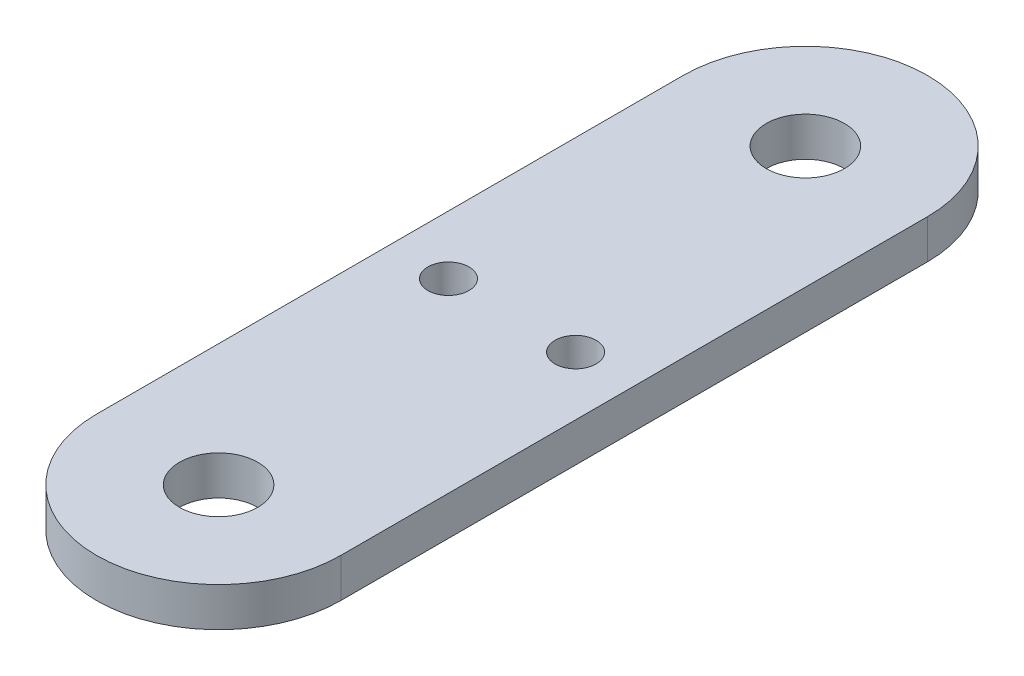
SolidWorks part; units mm, degrees
ref_plane "Front Plane" through (0, 0, 0) normal (0, 0, 1) x (1, 0, 0)
ref_plane "Top Plane" through (0, 0, 0) normal (0, 1, 0) x (1, 0, 0)
ref_plane "Right Plane" through (0, 0, 0) normal (1, 0, 0) x (0, 0, -1)
sketch "Sketch1" plane through (0, 0, 0) normal (0, 1, 0) x (1, 0, 0)
  line L0 (-6.5, 0) -> (6.5, 0) construction
  line L1 (0, 30) -> (0, -30) construction
  line L2 (12.5, -42.5) -> (-12.5, -42.5)
  line L3 (12.5, -42.5) -> (12.5, 42.5)
  line L4 (12.5, 42.5) -> (-12.5, 42.5)
  line L5 (-12.5, -42.5) -> (-12.5, 42.5)
  line L6 (12.5, -42.5) -> (-12.5, 42.5) construction
  line L7 (12.5, 42.5) -> (-12.5, -42.5) construction
  circle A0 centre (-6.5, 0) radius 2.1
  circle A1 centre (6.5, 0) radius 2.1
  circle A2 centre (0, -30) radius 4
  circle A3 centre (0, 30) radius 4
  circle A4 centre (0, 30) radius 12.5
  circle A5 centre (0, -30) radius 12.5
  point P4 (0, 0)
  dimension "D2" = 4.2
  dimension "D5" = 8
  dimension "D1" = 13
  dimension "D3" = 25
  dimension "D4" = 60
extrude "Boss-Extrude1" add sketch "Sketch1" along normal blind 4 contours A4 A3 | A5 L3 A4 L5 A1 A0 | A5 A2 region at (-8.5888, 0, 38.5888) region at (0, 0, 0) region at (0, 0, -17.8536)
equation "\"m3 hole\"= 3.2"
equation "\"m4 hole\"= 4.2"
equation "\"m5 hole\"= 5.2"
equation "\"m6 hole\"= 6.2"
equation "\"m8 hole\"= 8.2"
equation "\"m3 tapped\"= 2.5"
equation "\"m4 tapped\"= 3.3"
equation "\"m5 tapped\"= 4.2"
equation "\"m6 tapped\"= 5"
equation "\"m8 tapped\"= 6.8"
